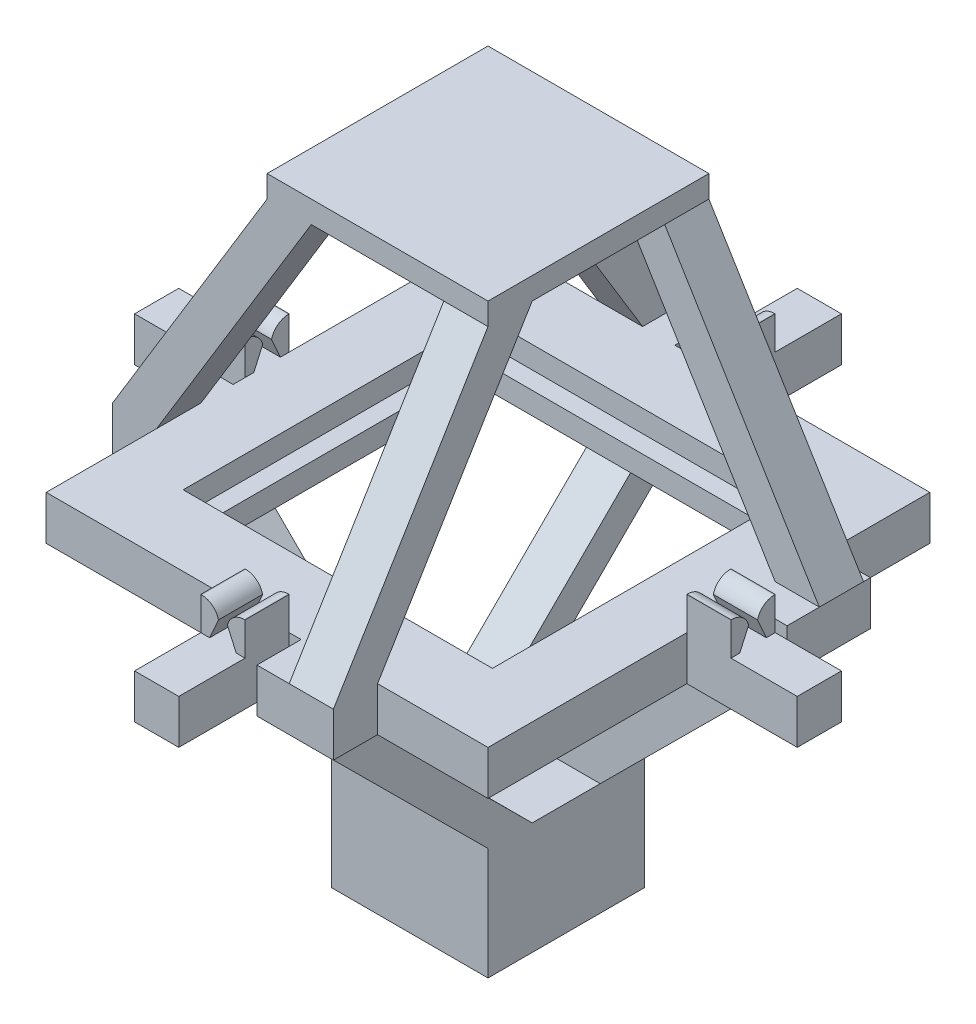
SolidWorks part; units mm, degrees
material "Delrin 2700 NC010, Low Viscosity Acetal Copolymer (SS)"
ref_plane "Front Plane" through (0, 0, 0) normal (0, 0, 1) x (1, 0, 0)
ref_plane "Top Plane" through (0, 0, 0) normal (0, 1, 0) x (1, 0, 0)
ref_plane "Right Plane" through (0, 0, 0) normal (1, 0, 0) x (0, 0, -1)
sketch "Sketch2" plane through (0, 0, 0) normal (0, 1, 0) x (1, 0, 0)
  line L1 (-50, -50) -> (50, -50)
  line L2 (-50, -50) -> (-50, 50)
  line L3 (-50, 50) -> (50, 50)
  line L4 (50, -50) -> (50, 50)
  line L5 (-50, -50) -> (50, 50) construction
  line L6 (-50, 50) -> (50, -50) construction
  point P0 (0, 0)
extrude "Boss-Extrude1" add sketch "Sketch2" along normal blind 5
sketch "Sketch3" plane through (0, 0, 0) normal (0, -1, 0) x (1, 0, 0)
  line L1 (-50, -50) -> (50, -50)
  line L2 (-50, -50) -> (-50, 50)
  line L3 (-50, 50) -> (50, 50)
  line L4 (50, -50) -> (50, 50)
  line L5 (-50, -50) -> (50, 50) construction
  line L6 (-50, 50) -> (50, -50) construction
  point P0 (0, 0)
extrude "Boss-Extrude2" add sketch "Sketch3" along normal blind 5
sketch "Sketch8" plane through (0, -5, 0) normal (0, -1, 0) x (1, 0, 0)
  circle A0 centre (0, 0) radius 5
extrude "Boss-Extrude7" add sketch "Sketch8" along normal blind 30
sketch "Sketch11" plane through (50, 0, 0) normal (1, 0, 0) x (0, 0, -1)
  line L0 (5, -5) -> (5, 12.5)
  line L3 (-5, -5) -> (5, -5)
  line L5 (5, 12.5) -> (1, 12.5)
  line L6 (1, 12.5) -> (1, 9.5)
  line L7 (-5, -5) -> (-5, 12.5)
  line L8 (-5, 12.5) -> (-1, 12.5)
  line L9 (-1, 12.5) -> (-1, 9.5)
  line L10 (-50, 5) -> (50, 5) construction
  line L11 (-1, 9.5) -> (-3, 5)
  line L12 (-3, 5) -> (3, 5)
  line L13 (3, 5) -> (1, 9.5)
  point P0 (0, 0)
  point P8 (3, 5)
  point P12 (-3, 5)
extrude "Boss-Extrude21" add sketch "Sketch11" along normal blind 10
fillet "Fillet14" radius 4 1 edges at (55, 12.5, -1)
fillet "Fillet13" radius 4 1 edges at (55, 12.5, 1)
sketch "Sketch24" plane through (60, 0, 0) normal (1, 0, 0) x (0, 0, -1)
  line L1 (-5, 5) -> (5, 5)
  line L2 (-5, 5) -> (-5, -5)
  line L3 (-5, -5) -> (5, -5)
  line L4 (5, 5) -> (5, -5)
  line L5 (-5, 5) -> (5, -5) construction
  line L6 (-5, -5) -> (5, 5) construction
  point P0 (0, 0)
extrude "Boss-Extrude22" add sketch "Sketch24" along normal blind 15
sketch "Sketch13" plane through (-50, 0, 0) normal (-1, 0, 0) x (0, 0, 1)
  line L0 (50, -5) -> (-50, -5) construction
  line L2 (-5, 12.5) -> (-5, -5)
  line L3 (-5, -5) -> (5, -5)
  line L4 (5, 12.5) -> (5, -5)
  line L5 (5, 12.5) -> (1, 12.5)
  line L6 (1, 12.5) -> (1, 9.5)
  line L7 (-5, 12.5) -> (-1, 12.5)
  line L8 (-1, 12.5) -> (-1, 9.5)
  line L9 (-1, 9.5) -> (-3, 5)
  line L10 (-3, 5) -> (3, 5)
  line L11 (3, 5) -> (1, 9.5)
  point P0 (0, 0)
  point P8 (-3, 5)
  point P13 (3, 5)
extrude "Boss-Extrude25" add sketch "Sketch13" along normal blind 10
sketch "Sketch26" plane through (-60, 0, 0) normal (-1, 0, 0) x (0, 0, 1)
  line L0 (-5, -5) -> (5, -5) construction
  line L1 (-5, 5) -> (5, 5)
  line L2 (-5, 5) -> (-5, -5)
  line L3 (-5, -5) -> (5, -5)
  line L4 (5, 5) -> (5, -5)
  line L5 (-5, 5) -> (5, -5) construction
  line L6 (-5, -5) -> (5, 5) construction
  line L7 (-5, -5) -> (5, -5) construction
  point P0 (0, 0)
extrude "Boss-Extrude26" add sketch "Sketch26" along normal blind 15
fillet "Fillet18" radius 4 1 edges at (-55, 12.5, 1)
fillet "Fillet17" radius 4 1 edges at (-55, 12.5, -1)
sketch "Sketch14" plane through (0, 0, -50) normal (0, 0, -1) x (-1, 0, 0)
  line L0 (-5, 12.5) -> (-1, 12.5)
  line L2 (-5, 12.5) -> (-5, -5)
  line L3 (-5, -5) -> (5, -5)
  line L4 (5, 12.5) -> (5, -5)
  line L5 (5, 12.5) -> (1, 12.5)
  line L6 (-1, 12.5) -> (-1, 9.5)
  line L7 (1, 12.5) -> (1, 9.5)
  line L8 (-50, 5) -> (50, 5) construction
  line L9 (-1, 9.5) -> (-3, 5)
  line L10 (-3, 5) -> (3, 5)
  line L11 (3, 5) -> (1, 9.5)
  point P0 (0, 0)
  point P11 (3, 5)
  point P12 (-3, 5)
extrude "Boss-Extrude23" add sketch "Sketch14" along normal blind 10
sketch "Sketch25" plane through (0, 0, -60) normal (0, 0, -1) x (-1, 0, 0)
  line L1 (-5, 5) -> (5, 5)
  line L2 (-5, 5) -> (-5, -5)
  line L3 (-5, -5) -> (5, -5)
  line L4 (5, 5) -> (5, -5)
  line L5 (-5, 5) -> (5, -5) construction
  line L6 (-5, -5) -> (5, 5) construction
  point P0 (0, 0)
extrude "Boss-Extrude24" add sketch "Sketch25" along normal blind 15
fillet "Fillet15" radius 4 1 edges at (-1, 12.5, -55)
fillet "Fillet16" radius 4 1 edges at (1, 12.5, -55)
sketch "Sketch12" plane through (0, 0, 50) normal (0, 0, 1) x (1, 0, 0)
  line L0 (50, -5) -> (-50, -5) construction
  line L2 (-5, 12.5) -> (-5, -5)
  line L3 (-5, -5) -> (5, -5)
  line L4 (5, 12.5) -> (5, -5)
  line L5 (5, 12.5) -> (1, 12.5)
  line L6 (1, 12.5) -> (1, 9.5)
  line L7 (-5, -5) -> (5, -5) construction
  line L8 (-5, 12.5) -> (-1, 12.5)
  line L9 (-1, 12.5) -> (-1, 9.5)
  line L10 (-1, 9.5) -> (-3, 5)
  line L11 (-3, 5) -> (3, 5)
  line L12 (3, 5) -> (1, 9.5)
  point P0 (0, 0)
  point P10 (-3, 5)
  point P15 (3, 5)
extrude "Boss-Extrude10" add sketch "Sketch12" along normal blind 10
fillet "Fillet19" radius 4 1 edges at (-1, 12.5, 55)
sketch "Sketch27" plane through (0, 0, 60) normal (0, 0, 1) x (1, 0, 0)
  line L1 (-5, 5) -> (5, 5)
  line L2 (-5, 5) -> (-5, -5)
  line L3 (-5, -5) -> (5, -5)
  line L4 (5, 5) -> (5, -5)
  line L5 (-5, 5) -> (5, -5) construction
  line L6 (-5, -5) -> (5, 5) construction
  point P0 (0, 0)
extrude "Boss-Extrude27" add sketch "Sketch27" along normal blind 15
fillet "Fillet20" radius 4 1 edges at (1, 12.5, 55)
ref_plane "Plane4" through (0, 72.5, 0) normal (0, 1, 0) x (1, 0, 0)
ref_plane "Plane5" through (0, -72.5, 0) normal (0, 1, 0) x (1, 0, 0)
sketch "Sketch62" plane through (0, -5, 0) normal (0, -1, 0) x (1, 0, 0)
  circle A0 centre (0, 0) radius 11.2235
extrude "Cut-Extrude3" cut sketch "Sketch62" along normal blind 30
sketch "Sketch64" plane through (0, -72.5, 0) normal (0, 1, 0) x (1, 0, 0)
  line L2 (17.7, 17.7) -> (-17.7, 17.7)
  line L3 (17.7, 17.7) -> (17.7, -17.7)
  line L4 (17.7, -17.7) -> (-17.7, -17.7)
  line L5 (-17.7, 17.7) -> (-17.7, -17.7)
  line L6 (17.7, 17.7) -> (-17.7, -17.7) construction
  line L7 (17.7, -17.7) -> (-17.7, 17.7) construction
  point P1 (0, 0)
extrude "Boss-Extrude53" add sketch "Sketch64" along normal blind 25.4 separate body
sketch "Sketch66" plane through (0, -72.5, 0) normal (0, -1, 0) x (-1, 0, 0)
  line L1 (12.7, -12.7) -> (-12.7, -12.7)
  line L2 (12.7, -12.7) -> (12.7, 12.7)
  line L3 (12.7, 12.7) -> (-12.7, 12.7)
  line L4 (-12.7, -12.7) -> (-12.7, 12.7)
  line L5 (12.7, -12.7) -> (-12.7, 12.7) construction
  line L6 (12.7, 12.7) -> (-12.7, -12.7) construction
  point P0 (0, 0)
extrude "Cut-Extrude4" cut sketch "Sketch66" against normal blind 12.7
ref_plane "Plane6" through (0, 67.5, 0) normal (0, 1, 0) x (1, 0, 0)
sketch "Sketch67" plane through (0, 67.5, 0) normal (0, 1, 0) x (1, 0, 0)
  line L1 (-25, 25) -> (25, 25)
  line L2 (-25, 25) -> (-25, -25)
  line L3 (-25, -25) -> (25, -25)
  line L4 (25, 25) -> (25, -25)
  line L5 (-25, 25) -> (25, -25) construction
  line L6 (-25, -25) -> (25, 25) construction
  point P0 (0, 0)
extrude "Boss-Extrude54" add sketch "Sketch67" against normal blind 5 separate body
sketch "Sketch68" plane through (0, 0, 50) normal (0, 0, 1) x (1, 0, 0)
  line L0 (5, 5) -> (50, 5) construction
  line L1 (50, -5) -> (5, -5) construction
  line L2 (7.7, -5) -> (25, -5)
  line L3 (25, -5) -> (25, 5)
  line L4 (25, 5) -> (7.7, 5)
  line L5 (7.7, 5) -> (7.7, -5)
  point P0 (25, 5)
  point P1 (15, 5)
  point P4 (15, 5)
  point P5 (17.7, -5)
  point P6 (7.7, -5)
extrude "Boss-Extrude55" add sketch "Sketch68" along normal blind 10
sketch "Sketch69" plane through (50, 0, 0) normal (1, 0, 0) x (0, 0, -1)
  line L0 (5, 5) -> (50, 5) construction
  line L1 (26.5525, 5) -> (9.2525, 5)
  line L2 (9.2525, -5) -> (9.2525, 5)
  line L3 (50, -5) -> (5, -5) construction
  line L4 (9.2525, -5) -> (26.5525, -5)
  line L5 (26.5525, -5) -> (26.5525, 5)
  point P0 (26.5525, 5)
extrude "Boss-Extrude56" add sketch "Sketch69" along normal blind 10
sketch "Sketch70" plane through (0, 0, -50) normal (0, 0, -1) x (-1, 0, 0)
  line L0 (5, 5) -> (50, 5) construction
  line L1 (25, 5) -> (7.7, 5)
  line L2 (7.7, 5) -> (7.7, -5)
  line L3 (50, -5) -> (5, -5) construction
  line L4 (7.7, -5) -> (25, -5)
  line L5 (25, -5) -> (25, 5)
  point P0 (25, 5)
extrude "Boss-Extrude57" add sketch "Sketch70" along normal blind 10
sketch "Sketch74" plane through (-50, 0, 0) normal (-1, 0, 0) x (0, 0, 1)
  line L0 (5, 5) -> (50, 5) construction
  line L1 (25, 5) -> (7.7, 5)
  line L2 (7.7, 5) -> (7.7, -5)
  line L3 (50, -5) -> (5, -5) construction
  line L4 (7.7, -5) -> (25, -5)
  line L5 (25, -5) -> (25, 5)
  point P0 (25, 5)
extrude "Boss-Extrude58" add sketch "Sketch74" along normal blind 10
sketch "Sketch76" plane through (-17.7, 0, 0) normal (-1, 0, 0) x (0, 0, 1)
  line L0 (-17.7, -47.1) -> (-60, -5)
  line L1 (-60, -5) -> (-50, -5)
  line L2 (-60, -5) -> (-50, -5) construction
  line L3 (-50, -5) -> (-7.7, -47.1)
  line L4 (-17.7, -47.1) -> (17.7, -47.1) construction
  line L5 (-7.7, -47.1) -> (-17.7, -47.1)
extrude "Boss-Extrude59" add sketch "Sketch76" against normal blind 10
sketch "Sketch77" plane through (-25, 0, 0) normal (-1, 0, 0) x (0, 0, 1)
  line L0 (-25, 62.5) -> (-60, 5)
  line L1 (-60, 5) -> (-50, 5)
  line L2 (-25, 62.5) -> (-15, 62.5)
  line L3 (-25, 62.5) -> (25, 62.5) construction
  line L4 (-15, 62.5) -> (-50, 5)
extrude "Boss-Extrude60" add sketch "Sketch77" against normal blind 10
sketch "Sketch78" plane through (0, 0, 17.7) normal (0, 0, 1) x (1, 0, 0)
  line L0 (-17.7, -47.1) -> (-60, -5)
  line L1 (-60, -5) -> (-50, -5)
  line L2 (-50, -5) -> (-7.7, -47.1)
  line L3 (-7.7, -47.1) -> (-17.7, -47.1)
extrude "Boss-Extrude61" add sketch "Sketch78" against normal blind 10
sketch "Sketch79" plane through (0, 0, 25) normal (0, 0, 1) x (1, 0, 0)
  line L0 (-25, 62.5) -> (-60, 5)
  line L1 (-60, 5) -> (-50, 5)
  line L2 (-50, 5) -> (-15, 62.5)
  line L3 (-15, 62.5) -> (-25, 62.5)
extrude "Boss-Extrude62" add sketch "Sketch79" against normal blind 10
sketch "Sketch82" plane through (17.7, 0, 0) normal (1, 0, 0) x (0, 0, -1)
  line L0 (-60, -5) -> (-17.7, -47.1)
  line L1 (-17.7, -47.1) -> (-7.7, -47.1)
  line L2 (-7.7, -47.1) -> (-50, -5)
  line L3 (-50, -5) -> (-60, -5)
extrude "Boss-Extrude63" add sketch "Sketch82" against normal blind 10
sketch "Sketch83" plane through (25, 0, 0) normal (1, 0, 0) x (0, 0, -1)
  line L0 (-25, 62.5) -> (-60, 5)
  line L1 (-60, 5) -> (-50, 5)
  line L2 (-50, 5) -> (-15, 62.5)
  line L3 (-15, 62.5) -> (-25, 62.5)
extrude "Boss-Extrude64" add sketch "Sketch83" against normal blind 10
sketch "Sketch85" plane through (50, 0, 0) normal (1, 0, 0) x (0, 0, -1)
  line L0 (5, 5) -> (9.2525, 5) construction
  line L1 (25, 5) -> (7.7, 5)
  line L2 (7.7, 5) -> (7.7, -5)
  line L4 (50, -5) -> (26.5525, -5) construction
  line L5 (7.7, -5) -> (25, -5)
  line L6 (25, -5) -> (25, 5)
  point P0 (25, 5)
extrude "Boss-Extrude65" add sketch "Sketch85" along normal blind 10
sketch "Sketch86" plane through (0, 0, -25) normal (0, 0, -1) x (-1, 0, 0)
  line L0 (-25, 62.5) -> (-60, 5)
  line L1 (-60, 5) -> (-50, 5)
  line L2 (-50, 5) -> (-15, 62.5)
  line L3 (-15, 62.5) -> (-25, 62.5)
extrude "Boss-Extrude66" add sketch "Sketch86" against normal blind 10
sketch "Sketch89" plane through (0, 0, -17.7) normal (0, 0, -1) x (-1, 0, 0)
  line L0 (-60, -5) -> (-50, -5)
  line L1 (-50, -5) -> (-7.7, -47.1)
  line L2 (-7.7, -47.1) -> (-17.7, -47.1)
  line L3 (-17.7, -47.1) -> (-60, -5)
extrude "Boss-Extrude67" add sketch "Sketch89" against normal blind 10
sketch "Sketch90" plane through (0, 5, 0) normal (0, 1, 0) x (1, 0, 0)
  line L1 (-35, 34) -> (35, 34)
  line L2 (-35, 34) -> (-35, -34)
  line L3 (-35, -34) -> (35, -34)
  line L4 (35, 34) -> (35, -34)
  line L5 (-35, 34) -> (35, -34) construction
  line L6 (-35, -34) -> (35, 34) construction
  point P0 (0, 0)
extrude "Cut-Extrude5" cut sketch "Sketch90" against normal blind 5
sketch "Sketch91" plane through (0, 0, 0) normal (0, 1, 0) x (1, 0, 0)
  line L1 (-31, 30) -> (31, 30)
  line L2 (-31, 30) -> (-31, -30)
  line L3 (-31, -30) -> (31, -30)
  line L4 (31, 30) -> (31, -30)
  line L5 (-31, 30) -> (31, -30) construction
  line L6 (-31, -30) -> (31, 30) construction
  point P0 (0, 0)
extrude "Cut-Extrude6" cut sketch "Sketch91" against normal blind 5
